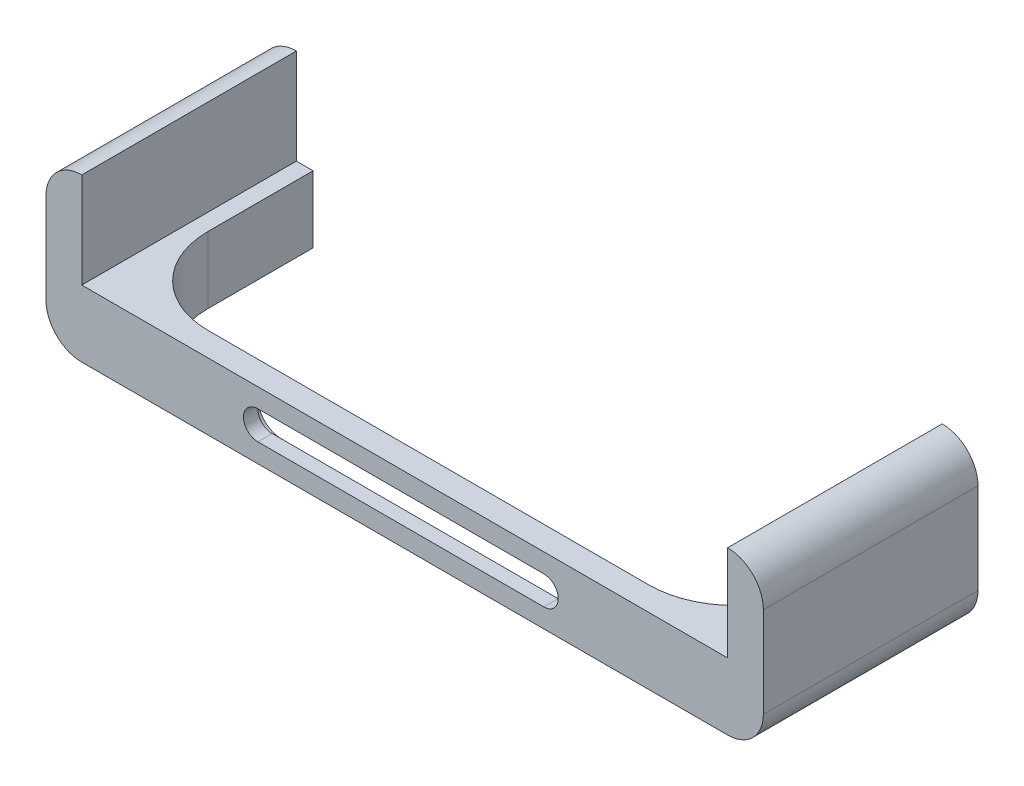
SolidWorks part; units mm, degrees
ref_plane "Front Plane" through (0, 0, 0) normal (0, 0, 1) x (1, 0, 0)
ref_plane "Top Plane" through (0, 0, 0) normal (0, 1, 0) x (1, 0, 0)
ref_plane "Right Plane" through (0, 0, 0) normal (1, 0, 0) x (0, 0, -1)
sketch "Sketch1" plane through (0, 0, 0) normal (0, 0, 1) x (1, 0, 0)
  line L5 (67.7, -325.2) -> (75.2, -325.2)
  line L6 (75.2, -325.2) -> (75.2, -359.2)
  line L15 (75.2, -359.2) -> (-75.2, -359.2)
  line L18 (-75.2, -359.2) -> (-75.2, -325.2)
  line L19 (-75.2, -325.2) -> (-67.7, -325.2)
  line L20 (-67.7, -325.2) -> (-67.7, -345.2)
  line L21 (-67.7, -345.2) -> (67.7, -345.2)
  line L22 (67.7, -345.2) -> (67.7, -325.2)
  line L23 (67.5, -345) -> (67.5, 0) construction
  line L24 (57.5, -345) -> (67.5, -345) construction
  line L25 (-67.5, -345) -> (-67.5, 0) construction
  dimension "D1" = 0.2
  dimension "D2" = 0.2
  dimension "D3" = 0.2
  dimension "D4" = 20
  dimension "D5" = 7.5
  dimension "D6" = 14
extrude "Boss-Extrude1" add sketch "Sketch1" against normal blind 5
sketch "Sketch2" plane through (0, 0, -5) normal (0, 0, -1) x (-1, 0, 0)
  line L0 (67.7, -325.2) -> (75.2, -325.2)
  line L1 (75.2, -325.2) -> (75.2, -359.2)
  line L2 (75.2, -359.2) -> (64.2, -359.2)
  line L3 (75.2, -359.2) -> (-75.2, -359.2) construction
  line L4 (64.2, -359.2) -> (64.2, -345.2)
  line L5 (-67.7, -345.2) -> (67.7, -345.2) construction
  line L6 (64.2, -345.2) -> (67.7, -345.2)
  line L7 (67.7, -345.2) -> (67.7, -325.2)
  line L8 (-75.2, -359.2) -> (-75.2, -325.2)
  line L9 (-75.2, -325.2) -> (-67.7, -325.2)
  line L10 (-67.7, -325.2) -> (-67.7, -345.2)
  line L11 (-67.7, -345.2) -> (-64.2, -345.2)
  line L12 (-64.2, -345.2) -> (-64.2, -359.2)
  line L13 (-64.2, -359.2) -> (-75.2, -359.2)
  dimension "D1" = 11
extrude "Boss-Extrude2" add sketch "Sketch2" along normal blind 40
sketch "Sketch3" plane through (0, 0, -5) normal (0, 0, -1) x (-1, 0, 0)
  line L0 (-29.2, -352.2) -> (30.8, -352.2) construction
  line L1 (-29.2, -347.2) -> (30.8, -347.2)
  line L2 (-29.2, -357.2) -> (30.8, -357.2)
  line L4 (64.2, -359.2) -> (-64.2, -359.2) construction
  line L7 (-64.2, -359.2) -> (-64.2, -345.2) construction
  arc A0 (-29.2, -347.2) -> (-29.2, -357.2) centre (-29.2, -352.2) ccw
  arc A1 (30.8, -357.2) -> (30.8, -347.2) centre (30.8, -352.2) ccw
  point P2 (0.8, -352.2)
  dimension "D1" = 5
  dimension "D2" = 7
  dimension "D3" = 65
  dimension "D4" = 60
extrude "Cut-Extrude1" cut sketch "Sketch3" against normal blind 2
sketch "Sketch4" plane through (0, 0, -3) normal (0, 0, -1) x (-1, 0, 0)
  line L0 (-29.2, -352.2) -> (30.8, -352.2) construction
  line L1 (-29.2, -349.2) -> (30.8, -349.2)
  line L2 (-29.2, -355.2) -> (30.8, -355.2)
  arc A0 (-29.2, -349.2) -> (-29.2, -355.2) centre (-29.2, -352.2) ccw
  arc A1 (30.8, -355.2) -> (30.8, -349.2) centre (30.8, -352.2) ccw
  point P4 (0.8, -352.2)
  dimension "D1" = 3
extrude "Cut-Extrude2" cut sketch "Sketch4" against normal through all
fillet "Fillet1" radius 18 2 edges at (-64.2, -352.2, -5) (64.2, -352.2, -5)
fillet "Fillet2" radius 7.5 4 edges at (75.2, -325.2, -22.5) (-75.2, -325.2, -22.5) (-75.2, -359.2, -22.5) (75.2, -359.2, -22.5)
